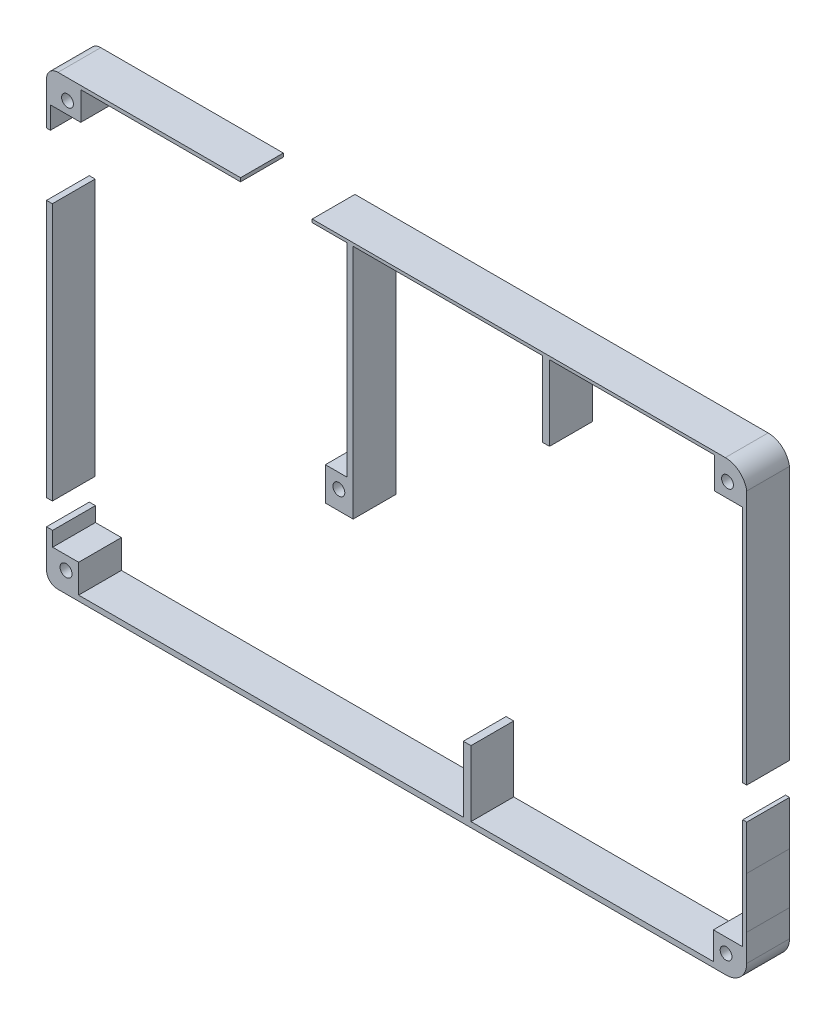
SolidWorks part; units mm, degrees
ref_plane "Front Plane" through (0, 0, 0) normal (0, 0, 1) x (1, 0, 0)
ref_plane "Top Plane" through (0, 0, 0) normal (0, 1, 0) x (1, 0, 0)
ref_plane "Right Plane" through (0, 0, 0) normal (1, 0, 0) x (0, 0, -1)
sketch "Sketch1" plane through (0, 0, 0) normal (0, 0, 1) x (1, 0, 0)
  line L8 (59.8585, -48.2256) -> (59.8392, -48.6176) construction
  line L17 (-71.1395, 21.4284) -> (-70.4179, 21.4284)
  line L18 (-71.1395, 21.4284) -> (-71.1395, 29.4179)
  line L20 (-70.4179, 21.4284) -> (-70.4179, 25.5609)
  line L21 (-71.1395, 9.7254) -> (-70.0449, 9.7254)
  line L22 (-71.1395, 9.7254) -> (-71.1395, -38.4528)
  line L23 (-71.1395, -38.4528) -> (-70.0449, -38.4528)
  line L24 (-70.0449, 9.7254) -> (-70.0449, -38.4528)
  line L25 (-69.9903, -43.1609) -> (-71.1395, -43.1609)
  line L26 (-69.9903, -43.1609) -> (-69.9903, -45.9026)
  line L28 (-71.1395, -43.1609) -> (-71.1395, -50.1652)
  line L29 (-69.1032, -52.2259) -> (55.8585, -52.2259)
  line L31 (-65.1271, -51.2289) -> (6.8368, -51.2289)
  line L34 (59.8488, -48.4216) -> (59.8488, -43.3759)
  line L37 (59.8585, -9.8647) -> (59.8585, -48.2256) construction
  line L39 (59.8585, -33.8318) -> (59.8585, -25.5099)
  line L40 (59.8585, -25.5099) -> (59.1103, -25.5099)
  line L41 (59.1103, -33.8318) -> (59.1103, -25.5099)
  line L42 (-34.8375, 31.5424) -> (-68.9905, 31.5424)
  line L43 (59.0464, -19.5201) -> (59.8585, -19.5201)
  line L44 (59.0464, -19.5201) -> (59.0464, -5.8076)
  line L46 (59.8585, -19.5201) -> (59.8585, -5.8076)
  line L48 (59.8585, 9.6924) -> (59.8585, 28.1302)
  line L50 (59.0641, 1.081) -> (59.0641, 25.122)
  line L52 (-64.7299, 25.5609) -> (-64.7299, 30.8683)
  line L53 (-64.7299, 30.8683) -> (-34.8375, 30.8683)
  line L54 (-34.8375, 31.5424) -> (-34.8375, 30.8683)
  line L56 (-21.4375, 31.544) -> (-21.4375, 30.9626)
  line L57 (-21.4375, 30.9626) -> (-14.9062, 30.9626)
  line L59 (-21.4375, 31.544) -> (55.8585, 31.544)
  line L60 (59.0641, 1.081) -> (59.0464, -5.8076)
  line L61 (59.8585, -5.8076) -> (59.8585, 9.6924)
  line L63 (59.8488, -43.3759) -> (59.8585, -33.8318)
  line L64 (-64.7299, 25.5609) -> (-70.4179, 25.5609)
  line L65 (58.7501, -46.0836) -> (53.6215, -46.0836)
  line L66 (53.6215, -46.0836) -> (53.6215, -51.2289)
  line L67 (-69.9903, -45.9026) -> (-65.1271, -45.9026)
  line L68 (-65.1271, -45.9026) -> (-65.1271, -51.2289)
  line L69 (8.2679, -51.2289) -> (53.6215, -51.2289)
  line L71 (8.2679, -51.2289) -> (8.2679, -38.9189)
  line L72 (8.2679, -38.9189) -> (6.8368, -38.9189)
  line L73 (6.8368, -51.2289) -> (6.8368, -38.9189)
  line L74 (-13.7751, 30.9626) -> (21.6916, 30.9626)
  line L76 (-14.9062, 30.9626) -> (-14.9062, -7.017)
  line L78 (-13.7751, 30.9626) -> (-13.7751, -5.8076)
  line L79 (59.1103, -33.8318) -> (59.1103, -46.0836)
  line L80 (59.1103, -46.0836) -> (58.7501, -46.0836)
  line L81 (53.7945, 30.9626) -> (53.7945, 25.122)
  line L82 (53.7945, 25.122) -> (59.0641, 25.122)
  line L83 (22.9629, 30.9626) -> (53.7945, 30.9626)
  line L85 (21.6916, 30.9626) -> (21.6916, 16.9135)
  line L86 (21.6916, 16.9135) -> (22.9629, 16.9135)
  line L87 (22.9629, 30.9626) -> (22.9629, 16.9135)
  line L88 (-18.9701, -7.017) -> (-14.9062, -7.017)
  line L90 (-18.9701, -7.017) -> (-18.9701, -13.2403)
  line L91 (-18.9701, -13.2403) -> (-13.7751, -13.2403)
  line L92 (-13.7751, -6.6477) -> (-13.7751, -13.2403)
  line L93 (-13.7751, -5.8076) -> (-13.7751, -6.6477)
  arc A0 (-71.1395, 29.4179) -> (-68.9905, 31.5424) centre (-69.0149, 29.4179) cw
  arc A5 (55.8585, 31.544) -> (59.8585, 28.1302) centre (55.8585, 27.4937) cw
  arc A10 (59.8488, -48.4216) -> (55.8585, -52.2259) centre (56.0403, -48.4216) cw
  arc A12 (-71.1395, -50.1652) -> (-69.1032, -52.2259) centre (-69.0787, -50.1652) ccw
  circle A14 centre (-67.2125, 27.8324) radius 1.1
  circle A15 centre (-16.4474, -9.7454) radius 1.1087
  circle A16 centre (-67.4891, -48.4216) radius 1.121
  circle A17 centre (55.9875, -48.7176) radius 1.1
  circle A18 centre (56.2625, 27.8324) radius 1.1
extrude "Boss-Extrude3" add sketch "Sketch1" along normal blind 8
